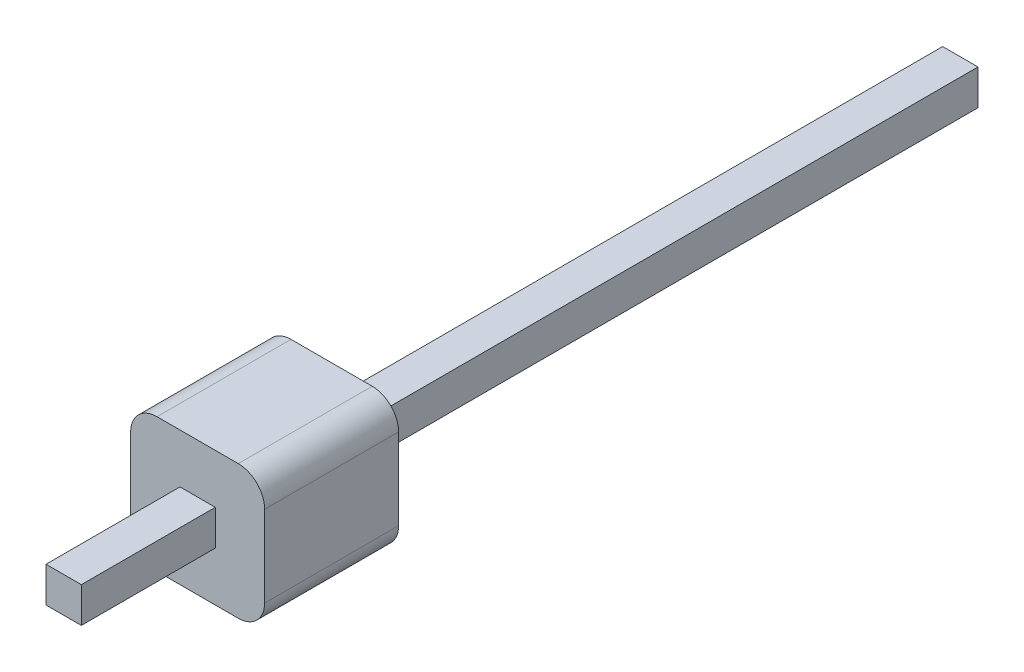
SolidWorks part; units mm, degrees
ref_plane "前视基准面" through (0, 0, 0) normal (0, 0, 1) x (1, 0, 0)
ref_plane "上视基准面" through (0, 0, 0) normal (0, 1, 0) x (1, 0, 0)
ref_plane "右视基准面" through (0, 0, 0) normal (1, 0, 0) x (0, 0, -1)
sketch "草图1" plane through (0, 0, 0) normal (0, 0, 1) x (1, 0, 0)
  line L0 (0, 5.3599) -> (0, -8.0108) construction
  line L1 (-1.27, -0.0191) -> (1.27, -0.0191)
  line L2 (-1.27, -0.0191) -> (-1.27, -2.5591)
  line L3 (-1.27, -2.5591) -> (1.27, -2.5591)
  line L4 (1.27, -0.0191) -> (1.27, -2.5591)
  dimension "D1" = 2.54
  dimension "D2" = 2.54
extrude "拉伸1" add sketch "草图1" along normal blind 2.54
ref_plane "基准面1" through (0, 0, 5.08) normal (0, 0, -1) x (-1, 0, 0)
sketch "草图2" plane through (0, 0, 5.08) normal (0, 0, -1) x (-1, 0, 0)
  line L0 (-1.27, -1.2891) -> (1.27, -1.2891) construction
  line L1 (-1.27, -2.5591) -> (-1.27, -0.0191) construction
  line L2 (1.27, -0.0191) -> (1.27, -2.5591) construction
  line L3 (0, 1.9407) -> (0, -4.2425) construction
  line L5 (-0.335, -0.9541) -> (0.335, -0.9541)
  line L6 (-0.335, -0.9541) -> (-0.335, -1.6241)
  line L7 (-0.335, -1.6241) -> (0.335, -1.6241)
  line L8 (0.335, -0.9541) -> (0.335, -1.6241)
  dimension "D1" = 0.67
  dimension "D2" = 0.67
sketch "草图3" plane through (0, 0, 0) normal (1, 0, 0) x (0, 0, -1)
  line L0 (11.92, -1.2991) -> (-5.08, -1.2991)
  line L1 (-5.08, 1.9407) -> (-5.08, -4.2425) construction
  line L8 (-2.54, -0.0191) -> (0, -0.0191) construction
  line L9 (0, -2.5591) -> (0, -0.0191) construction
  point P11 (2.54, -1.2991)
  dimension "D1" = 5.08
  dimension "D2" = 17
  dimension "D4" = 1.28
sweep "扫描1" add profiles "草图2" path "草图3"
fillet "圆角1" radius 0.5 4 edges at (1.27, -0.0191, 1.27) (1.27, -2.5591, 1.27) (-1.27, -2.5591, 1.27) (-1.27, -0.0191, 1.27)
